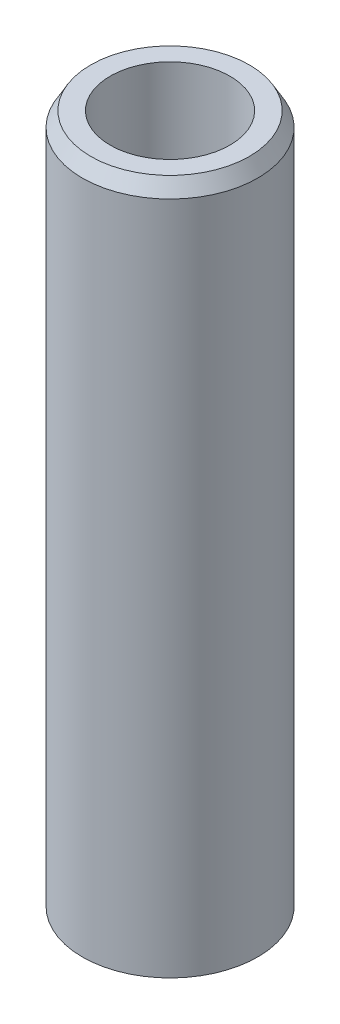
SolidWorks part; units mm, degrees
ref_plane "Front Plane" through (0, 0, 0) normal (0, 0, 1) x (1, 0, 0)
ref_plane "Top Plane" through (0, 0, 0) normal (0, 1, 0) x (1, 0, 0)
ref_plane "Right Plane" through (0, 0, 0) normal (1, 0, 0) x (0, 0, -1)
sketch "Sketch1" plane through (0, 0, 0) normal (0, 1, 0) x (1, 0, 0)
  circle A0 centre (0, 0) radius 32.5
  dimension "SHAFT_OD" = 65
extrude "Boss-Extrude1" add sketch "Sketch1" along normal blind 258.4237
sketch "Sketch2" plane through (0, 0, 0) normal (0, 1, 0) x (1, 0, 0)
  circle A0 centre (0, 0) radius 22.172
  dimension "BORE_D" = 44.344
extrude "Cut-Extrude1" cut sketch "Sketch2" along normal through all
chamfer "Chamfer1" distance 5.3916 angle 30 2 edges at (0, 258.4237, 32.5) (0, 0, 32.5) first distance on face at (0, 258.4237, 32.5) first distance on face at (0, 0, 22.172)
